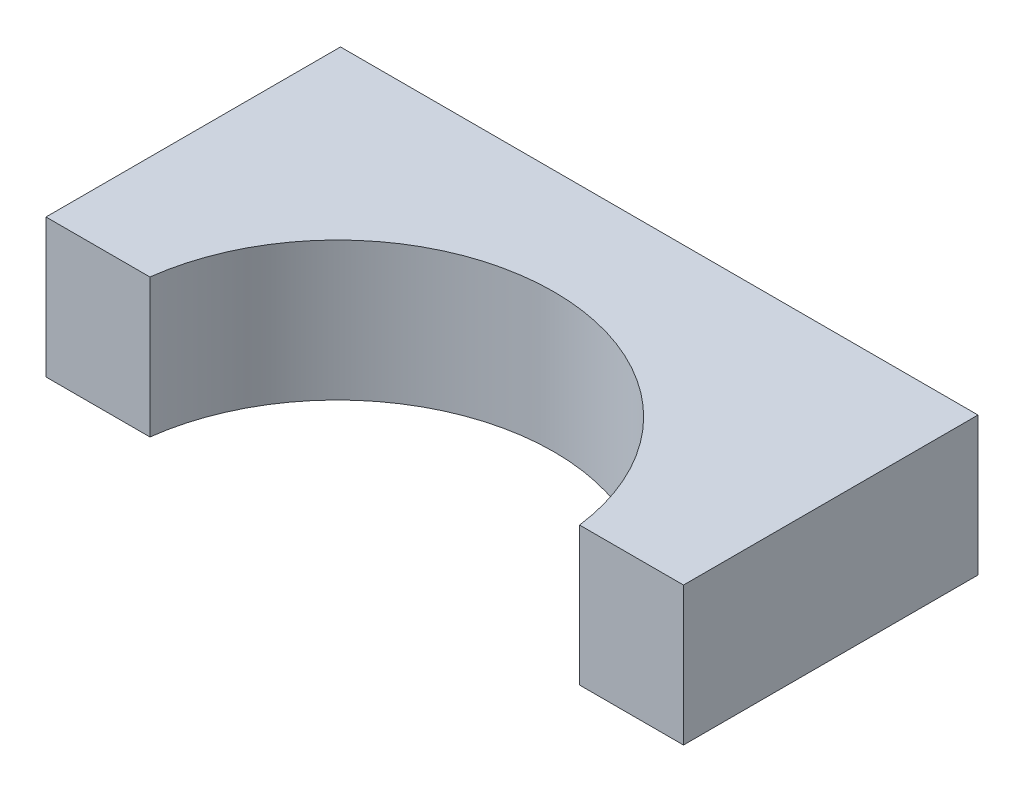
SolidWorks part; units mm, degrees
material "PLA"
ref_plane "Front" through (0, 0, 0) normal (0, 0, 1) x (1, 0, 0)
ref_plane "Top" through (0, 0, 0) normal (0, 1, 0) x (1, 0, 0)
ref_plane "Right" through (0, 0, 0) normal (1, 0, 0) x (0, 0, -1)
sketch "Sketch2" plane through (0, 0, 0) normal (0, 1, 0) x (1, 0, 0)
  line L0 (-14.986, -8.89) -> (-7.366, -8.89)
  line L1 (-14.986, 12.7) -> (31.75, 12.7)
  line L2 (-14.986, 12.7) -> (-14.986, -8.89)
  line L4 (31.75, 12.7) -> (31.75, -8.89)
  line L5 (24.13, -8.89) -> (31.75, -8.89)
  arc A3 (24.13, -8.89) -> (-7.366, -8.89) centre (8.382, -10.894) ccw
  point P0 (0, 0)
  dimension "D5" = 31.75
  dimension "D1" = 46.736
  dimension "D2" = 21.59
  dimension "D3" = 7.62
  dimension "D4" = 7.62
extrude "Boss-Extrude1" add sketch "Sketch2" against normal blind 10.16
sketch "Sketch6" plane through (0, 0, -12.7) normal (0, 0, -1) x (-1, 0, 0)
  line L0 (0, 0) -> (14.986, 0)
  line L1 (14.986, 0) -> (-31.75, 0)
  line L2 (-31.75, 0) -> (-8.382, 0)
  line L3 (-8.382, 0) -> (-8.382, -10.16)
  line L6 (-8.382, -5.08) -> (14.986, -5.08)
  line L7 (14.986, -10.16) -> (14.986, 0) construction
  line L8 (14.986, -5.08) -> (-31.75, -5.08)
  line L9 (-31.75, -10.16) -> (-31.75, 0) construction
  line L10 (-27.94, -5.08) -> (-8.382, -5.08)
  line L11 (-8.382, -5.08) -> (11.176, -5.08)
  circle A0 centre (-27.94, -5.08) radius 1.6002
  circle A1 centre (11.176, -5.08) radius 1.6002
  dimension "D2" = 3.2004
  dimension "D5" = 3.2004
  dimension "D1" = 23.368
  dimension "D3" = 19.558
  dimension "D4" = 19.558
extrude "Cut-Extrude1" cut sketch "Sketch6" against normal blind 4.064 contours L10 A0 L8 | L8 A0 L10 | L8 A1 L11 | L11 A1 L8 region at (-11.176, -4.4009, -12.7) region at (-11.176, -5.7591, -12.7) region at (27.94, -5.7591, -12.7) region at (27.94, -4.4009, -12.7)
